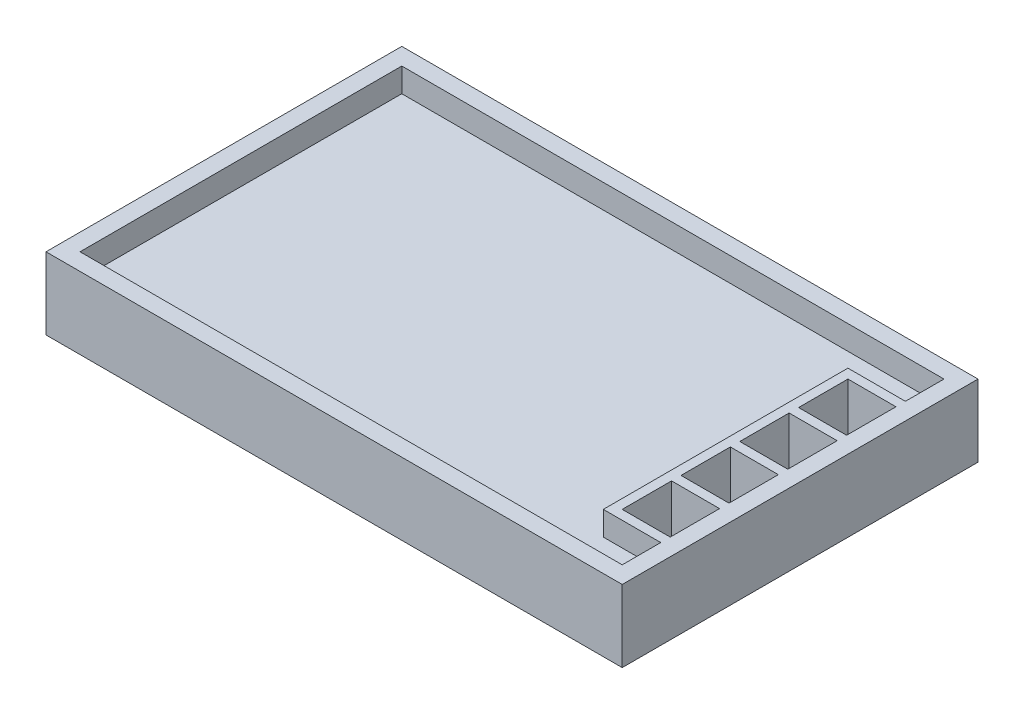
SolidWorks part; units mm, degrees
ref_plane "Front Plane" through (0, 0, 0) normal (0, 0, 1) x (1, 0, 0)
ref_plane "Top Plane" through (0, 0, 0) normal (0, 1, 0) x (1, 0, 0)
ref_plane "Right Plane" through (0, 0, 0) normal (1, 0, 0) x (0, 0, -1)
sketch "Sketch1" plane through (0, 0, 0) normal (0, 1, 0) x (1, 0, 0)
  line L1 (-272.4428, 257.4165) -> (337.1572, 257.4165)
  line L2 (-272.4428, 257.4165) -> (-272.4428, -118.9835)
  line L3 (-272.4428, -118.9835) -> (337.1572, -118.9835)
  line L4 (337.1572, 257.4165) -> (337.1572, -118.9835)
  dimension "D1" = 609.6
  dimension "D2" = 376.4
extrude "Boss-Extrude1" add sketch "Sketch1" against normal blind 76.2
sketch "Sketch2" plane through (0, 0, 0) normal (0, 1, 0) x (1, 0, 0)
  line L0 (-272.4428, 257.4165) -> (-272.4428, -118.9835) construction
  line L1 (-254.4428, 239.4165) -> (319.1572, 239.4165)
  line L2 (-254.4428, 239.4165) -> (-254.4428, -100.9835)
  line L3 (-254.4428, -100.9835) -> (319.1572, -100.9835)
  line L4 (319.1572, 239.4165) -> (319.1572, -100.9835)
  line L5 (-272.4428, -118.9835) -> (337.1572, -118.9835) construction
  line L6 (337.1572, -118.9835) -> (337.1572, 257.4165) construction
  line L7 (337.1572, 257.4165) -> (-272.4428, 257.4165) construction
  dimension "D1" = 18
  dimension "D2" = 18
  dimension "D3" = 18
  dimension "D4" = 18
extrude "Cut-Extrude1" cut sketch "Sketch2" against normal offset from surface (25.4 mm away) 25.4 up to face at (32.3572, 0, -69.2165)
sketch "Sketch3" plane through (0, -25.4, 0) normal (0, 1, 0) x (1, 0, 0)
  line L0 (384.8029, 69.2165) -> (-352.974, 69.2165) construction
  line L1 (-254.4428, 239.4165) -> (319.1572, 239.4165) construction
  line L2 (-254.4428, -100.9835) -> (319.1572, -100.9835) construction
  line L3 (319.1572, 239.4165) -> (319.1572, -100.9835) construction
  line L4 (319.1572, 188.6165) -> (268.3572, 188.6165)
  line L5 (319.1572, 188.6165) -> (319.1572, 136.4165)
  line L6 (319.1572, 136.4165) -> (268.3572, 136.4165)
  line L7 (268.3572, 188.6165) -> (268.3572, 136.4165)
  line L8 (319.1572, -100.9835) -> (319.1572, 239.4165) construction
  line L9 (319.1572, 126.4165) -> (268.3572, 126.4165)
  line L10 (319.1572, 126.4165) -> (319.1572, 74.2165)
  line L11 (319.1572, 74.2165) -> (268.3572, 74.2165)
  line L12 (268.3572, 126.4165) -> (268.3572, 74.2165)
  line L13 (319.1572, 64.2165) -> (268.3572, 64.2165)
  line L14 (319.1572, 64.2165) -> (319.1572, 12.0165)
  line L15 (319.1572, 12.0165) -> (268.3572, 12.0165)
  line L16 (268.3572, 64.2165) -> (268.3572, 12.0165)
  line L18 (319.1572, 2.0165) -> (268.3572, 2.0165)
  line L19 (319.1572, 2.0165) -> (319.1572, -50.1835)
  line L20 (319.1572, -50.1835) -> (268.3572, -50.1835)
  line L21 (268.3572, 2.0165) -> (268.3572, -50.1835)
  dimension "D1" = 10
  dimension "D2" = 10
  dimension "D3" = 10
  dimension "D4" = 50.8
  dimension "D5" = 50.8
extrude "Cut-Extrude2" cut sketch "Sketch3" against normal offset from surface (35.8 mm away) 15 up to face at (32.3572, -76.2, -69.2165)
sketch "Sketch7" plane through (0, -25.4, 0) normal (0, 1, 0) x (1, 0, 0)
  line L0 (319.1572, 198.6165) -> (258.3572, 198.6165)
  line L1 (319.1572, 239.4165) -> (319.1572, 188.6165) construction
  line L2 (258.3572, 198.6165) -> (258.3572, -60.1835)
  line L3 (258.3572, -60.1835) -> (319.1572, -60.1835)
  line L4 (319.1572, -50.1835) -> (319.1572, -100.9835) construction
  line L5 (319.1572, -60.1835) -> (319.1572, -50.1835)
  line L6 (319.1572, -50.1835) -> (268.3572, -50.1835)
  line L7 (268.3572, -50.1835) -> (268.3572, 2.0165)
  line L8 (268.3572, 2.0165) -> (319.1572, 2.0165)
  line L9 (319.1572, 2.0165) -> (319.1572, 12.0165)
  line L10 (319.1572, 12.0165) -> (268.3572, 12.0165)
  line L11 (268.3572, 12.0165) -> (268.3572, 64.2165)
  line L12 (268.3572, 64.2165) -> (319.1572, 64.2165)
  line L13 (319.1572, 64.2165) -> (319.1572, 74.2165)
  line L14 (319.1572, 74.2165) -> (268.3572, 74.2165)
  line L15 (268.3572, 74.2165) -> (268.3572, 126.4165)
  line L16 (268.3572, 126.4165) -> (319.1572, 126.4165)
  line L17 (319.1572, 126.4165) -> (319.1572, 136.4165)
  line L18 (319.1572, 136.4165) -> (268.3572, 136.4165)
  line L19 (268.3572, 136.4165) -> (268.3572, 188.6165)
  line L20 (268.3572, 188.6165) -> (319.1572, 188.6165)
  line L21 (319.1572, 188.6165) -> (319.1572, 198.6165)
  dimension "D1" = 10
  dimension "D2" = 10
  dimension "D3" = 10
extrude "Boss-Extrude2" add sketch "Sketch7" along normal up to surface (25.4 mm away) up to face at (32.3572, 0, -69.2165)
